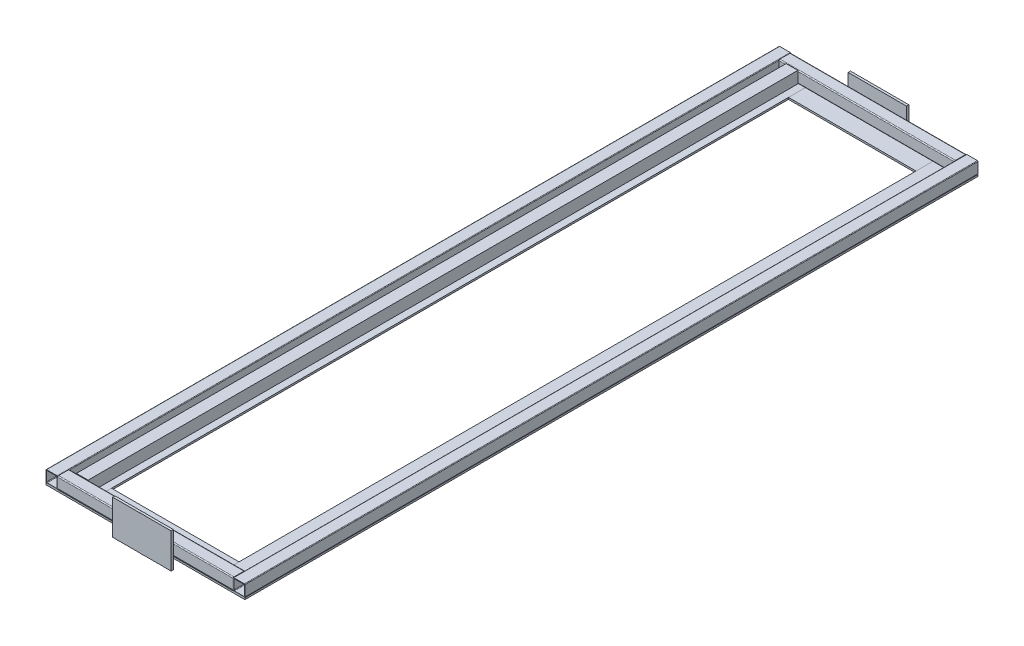
SolidWorks part; units mm, degrees
material "1023 碳钢板 (SS)"
ref_plane "前视基准面" through (0, 0, 0) normal (0, 0, 1) x (1, 0, 0)
ref_plane "上视基准面" through (0, 0, 0) normal (0, 1, 0) x (1, 0, 0)
ref_plane "右视基准面" through (0, 0, 0) normal (1, 0, 0) x (0, 0, -1)
sketch "草图1" plane through (0, 0, 0) normal (0, 0, 1) x (1, 0, 0)
  line L0 (-40, 45) -> (40, 45)
  line L1 (-45, 50) -> (45, 50)
  line L2 (-50, 45) -> (-50, -45)
  line L3 (-45, -50) -> (45, -50)
  line L4 (50, 45) -> (50, -45)
  line L5 (-50, 50) -> (50, -50) construction
  line L6 (-50, -50) -> (50, 50) construction
  line L7 (45, 40) -> (45, -40)
  line L8 (-40, -45) -> (40, -45)
  line L9 (-45, 40) -> (-45, -40)
  line L10 (-45, -45) -> (45, -45) construction
  line L11 (-45, 45) -> (-45, -45) construction
  line L12 (45, 45) -> (45, -45) construction
  line L13 (-45, 45) -> (45, 45) construction
  line L14 (-50, 50) -> (-50, -50) construction
  line L15 (-50, -50) -> (50, -50) construction
  line L16 (50, 50) -> (50, -50) construction
  line L17 (-50, 50) -> (50, 50) construction
  arc A0 (-40, -45) -> (-45, -40) centre (-40, -40) cw
  arc A1 (45, -40) -> (40, -45) centre (40, -40) cw
  arc A2 (40, 45) -> (45, 40) centre (40, 40) cw
  arc A3 (-40, 45) -> (-45, 40) centre (-40, 40) ccw
  arc A4 (-50, -45) -> (-45, -50) centre (-45, -45) ccw
  arc A5 (45, -50) -> (50, -45) centre (45, -45) ccw
  arc A6 (45, 50) -> (50, 45) centre (45, 45) cw
  arc A7 (-45, 50) -> (-50, 45) centre (-45, 45) ccw
  point P0 (0, 0)
  dimension "D4" = 5
  dimension "D5" = 5
  dimension "D1" = 100
  dimension "D2" = 100
  dimension "D3" = 5
extrude "凸台-拉伸1" add sketch "草图1" along normal blind 6265.6
pattern_linear "阵列(线性)1" count 2 spacing 1600 along (1, 0, 0) of bodies 106
sketch "草图2" plane through (50, 0, 0) normal (1, 0, 0) x (0, 0, -1)
  line L0 (-6265.6, -45) -> (-6265.6, 45) construction
  line L1 (-6173.6, -50) -> (-6257.6, -50)
  line L2 (-6165.6, -42) -> (-6165.6, 42)
  line L3 (-6173.6, 50) -> (-6257.6, 50)
  line L4 (-6265.6, -42) -> (-6265.6, 42)
  line L5 (-6165.6, -50) -> (-6265.6, 50) construction
  line L6 (-6165.6, 50) -> (-6265.6, -50) construction
  line L7 (-6265.6, 50) -> (0, 50) construction
  line L8 (-6265.6, -50) -> (0, -50) construction
  line L9 (-6175.6, 45) -> (-6255.6, 45)
  line L10 (-6260.6, -40) -> (-6260.6, 40)
  line L11 (-6175.6, -45) -> (-6255.6, -45)
  line L12 (-6170.6, -40) -> (-6170.6, 40)
  line L13 (-6260.6, -45) -> (-6260.6, 45) construction
  line L14 (-6170.6, -45) -> (-6260.6, -45) construction
  line L15 (-6170.6, -45) -> (-6170.6, 45) construction
  line L16 (-6170.6, 45) -> (-6260.6, 45) construction
  line L17 (-6165.6, -50) -> (-6265.6, -50) construction
  line L18 (-6265.6, -50) -> (-6265.6, 50) construction
  line L19 (-6165.6, -50) -> (-6165.6, 50) construction
  line L20 (-6165.6, 50) -> (-6265.6, 50) construction
  arc A0 (-6260.6, -40) -> (-6255.6, -45) centre (-6255.6, -40) ccw
  arc A1 (-6175.6, -45) -> (-6170.6, -40) centre (-6175.6, -40) ccw
  arc A2 (-6175.6, 45) -> (-6170.6, 40) centre (-6175.6, 40) cw
  arc A3 (-6255.6, 45) -> (-6260.6, 40) centre (-6255.6, 40) ccw
  arc A4 (-6257.6, -50) -> (-6265.6, -42) centre (-6257.6, -42) cw
  arc A5 (-6173.6, -50) -> (-6165.6, -42) centre (-6173.6, -42) ccw
  arc A6 (-6165.6, 42) -> (-6173.6, 50) centre (-6173.6, 42) ccw
  arc A7 (-6257.6, 50) -> (-6265.6, 42) centre (-6257.6, 42) ccw
  point P0 (-6215.6, 0)
  dimension "D3" = 5
  dimension "D4" = 8
  dimension "D1" = 100
  dimension "D2" = 5
extrude "凸台-拉伸2" add sketch "草图2" along normal up to surface (1500 mm away) separate body up to face at (1550, 0, 3132.8)
pattern_linear "阵列(线性)2" count 2 spacing 6165.6 along (0, 0, -1) of bodies 108
sketch "草图4" plane through (0, 0, 0) normal (0, 0, -1) x (-1, 0, 0)
  line L0 (50, 45) -> (50, -45) construction
  circle A0 centre (-790, 0) radius 150
  point P2 (50, 0)
  dimension "D1" = 300
  dimension "D2" = 840
extrude "凸台-拉伸4" add sketch "草图4" along normal blind 20 separate body
sketch "草图5" plane through (0, 0, 6265.6) normal (0, 0, 1) x (1, 0, 0)
  circle A0 centre (790, 0) radius 150
  dimension "D1" = 300
extrude "凸台-拉伸5" add sketch "草图5" along normal blind 20 separate body
sketch "草图6" plane through (0, 0, 6285.6) normal (0, 0, 1) x (1, 0, 0)
  circle A0 centre (790, 0) radius 140
  dimension "D1" = 280
extrude "切除-拉伸1" cut sketch "草图6" against normal blind 3
sketch "草图7" plane through (0, 0, -20) normal (0, 0, -1) x (-1, 0, 0)
  circle A0 centre (-790, 0) radius 90
  dimension "D1" = 180
extrude "切除-拉伸2" cut sketch "草图7" against normal blind 5
sketch "草图8" plane through (0, 0, -20) normal (0, 0, -1) x (-1, 0, 0)
  circle A0 centre (-790, 0) radius 127.5 construction
  circle A1 centre (-790, 127.5) radius 6.25
  dimension "D1" = 255
  dimension "D2" = 12.5
extrude "切除-拉伸3" cut sketch "草图8" against normal through all
pattern_circular "阵列(圆周)1" count 8 over 360 about axis through (790, 0, 6285.6) along (0, 0, -1) of "切除-拉伸3"
sketch "草图11" plane through (0, 0, -15) normal (0, 0, -1) x (-1, 0, 0)
  line L1 (-850, 30) -> (-730, 30)
  line L2 (-850, 30) -> (-850, -30)
  line L3 (-850, -30) -> (-730, -30)
  line L4 (-730, 30) -> (-730, -30)
  line L5 (-850, 30) -> (-730, -30) construction
  line L6 (-850, -30) -> (-730, 30) construction
  point P0 (-790, 0)
  dimension "D1" = 60
  dimension "D2" = 120
extrude "切除-拉伸5" [suppressed] cut sketch "草图11" against normal up to surface (115 mm away)
fillet "圆角1" [suppressed] radius 5
fillet "圆角2" [suppressed] radius 5
fillet "圆角3" [suppressed] radius 5
sketch "草图12" plane through (0, 50, 0) normal (0, 1, 0) x (1, 0, 0)
  line L0 (1555, -6265.6) -> (1555, 0) construction
  line L1 (50, -90) -> (1555, -90)
  line L2 (50, -90) -> (50, -2077.7459)
  line L3 (50, -2077.7459) -> (1555, -2077.7459)
  line L4 (1555, -90) -> (1555, -2077.7459)
extrude "凸台-拉伸8" [suppressed] add sketch "草图12" along normal blind 36 separate body
ref_axis "基准轴1" through (790, 0, 6285.6) along (0, 0, -1)
sketch "草图21" plane through (0, 0, -20) normal (0, 0, -1) x (-1, 0, 0)
  line L1 (-1040, 150) -> (-540, 150)
  line L2 (-1040, 150) -> (-1040, -150)
  line L3 (-1040, -150) -> (-540, -150)
  line L4 (-540, 150) -> (-540, -150)
  line L5 (-1040, 150) -> (-540, -150) construction
  line L6 (-1040, -150) -> (-540, 150) construction
  point P0 (-790, 0)
  dimension "D1" = 300
  dimension "D2" = 500
extrude "凸台-拉伸11" add sketch "草图21" against normal blind 20
sketch "草图22" plane through (0, 0, 6285.6) normal (0, 0, 1) x (1, 0, 0)
  line L0 (1040, 150) -> (1040, 42) construction
  line L1 (540, -148.5061) -> (1040, -148.5061)
  line L2 (540, -148.5061) -> (540, 148.5061)
  line L3 (540, 148.5061) -> (1040, 148.5061)
  line L4 (1040, -148.5061) -> (1040, 148.5061)
  line L5 (540, -148.5061) -> (1040, 148.5061) construction
  line L6 (540, 148.5061) -> (1040, -148.5061) construction
  point P0 (790, 0)
extrude "凸台-拉伸13" add sketch "草图22" against normal blind 20
ref_plane "基准面1" through (0, 0, 3132.8) normal (0, 0, 1) x (1, 0, 0)
ref_plane "基准面2" through (800, 0, 0) normal (-1, 0, 0) x (0, 0, 1)
sketch "草图23" plane through (0, 0, 100) normal (0, 0, 1) x (1, 0, 0)
  line L0 (800, 0) -> (550, 0) construction
  line L1 (1550, -50) -> (50, -50) construction
  line L2 (500, 50) -> (600, 50)
  line L3 (500, 50) -> (500, -50)
  line L4 (500, -50) -> (600, -50)
  line L5 (600, 50) -> (600, -50)
  line L6 (500, 50) -> (600, -50) construction
  line L7 (500, -50) -> (600, 50) construction
  line L8 (800, 0) -> (800, 362.3547) construction
  line L9 (1000, 50) -> (1100, 50)
  line L10 (1000, 50) -> (1000, -50)
  line L11 (1000, -50) -> (1100, -50)
  line L12 (1100, 50) -> (1100, -50)
  line L13 (1000, 50) -> (1100, -50) construction
  line L14 (1000, -50) -> (1100, 50) construction
  line L15 (800, 586.0493) -> (800, -586.0493) construction
  point P10 (1050, 0)
  dimension "D1" = 600
extrude "凸台-拉伸14" [suppressed] add sketch "草图23" along normal up to surface (6065.6 mm away)
sketch "草图24" plane through (0, -50, 0) normal (0, 1, 0) x (1, 0, 0)
  line L0 (540, 0) -> (50, 0) construction
  line L1 (1650, -6265.6) -> (1360, -6265.6)
  line L2 (1650, -6265.6) -> (1650, 0)
  line L3 (1650, 0) -> (1360, 0)
  line L4 (1360, -6265.6) -> (1360, 0)
  line L7 (1650, -6265.6) -> (1650, 0) construction
  line L8 (1645, -6265.6) -> (1650, -6265.6) construction
  dimension "D1" = 290
extrude "凸台-拉伸16" add sketch "草图24" against normal blind 15 separate body
sketch "草图26" [suppressed] plane through (950, 0, 0) normal (-1, 0, 0) x (0, 0, 1)
  line L0 (6165.6, -50) -> (100, -50) construction
  line L1 (632.8, -50) -> (732.8, -50)
  line L2 (632.8, -50) -> (632.8, 50)
  line L3 (632.8, 50) -> (732.8, 50)
  line L4 (732.8, -50) -> (732.8, 50)
  line L5 (6165.6, 50) -> (100, 50) construction
  line L6 (3132.8, -50) -> (3132.8, 50) construction
  line L7 (5632.8, -50) -> (5532.8, -50)
  line L8 (5632.8, -50) -> (5632.8, 50)
  line L9 (5632.8, 50) -> (5532.8, 50)
  line L10 (5532.8, -50) -> (5532.8, 50)
  line L11 (6265.6, 50) -> (0, 50) construction
  line L12 (6265.6, -50) -> (0, -50) construction
  line L13 (3082.8, 50) -> (3182.8, 50)
  line L14 (3082.8, 50) -> (3082.8, -50)
  line L15 (3082.8, -50) -> (3182.8, -50)
  line L16 (3182.8, 50) -> (3182.8, -50)
  line L17 (3082.8, 50) -> (3182.8, -50) construction
  line L18 (3082.8, -50) -> (3182.8, 50) construction
  point P17 (3132.8, 0)
  dimension "D1" = 5000
extrude "凸台-拉伸17" [suppressed] add sketch "草图26" along normal up to surface (400 mm away)
sketch "草图27" plane through (0, -50, 0) normal (0, -1, 0) x (1, 0, 0)
  line L1 (1360, 6265.6) -> (270, 6265.6)
  line L2 (1360, 6265.6) -> (1360, 6025.6)
  line L3 (1360, 6025.6) -> (270, 6025.6)
  line L4 (270, 6265.6) -> (270, 6025.6)
  line L5 (-50, 6265.6) -> (-50, 0) construction
  line L6 (1360, 0) -> (270, 0)
  line L7 (1360, 0) -> (1360, 240)
  line L8 (1360, 240) -> (270, 240)
  line L9 (270, 0) -> (270, 240)
  dimension "D1" = 240
  dimension "D2" = 320
extrude "凸台-拉伸18" add sketch "草图27" along normal blind 15 separate body
sketch "草图28" plane through (0, 0, 6165.6) normal (0, 0, -1) x (-1, 0, 0)
  line L0 (-1550, -50) -> (-50, -50) construction
  line L1 (-110, -50) -> (-210, -50)
  line L2 (-110, -50) -> (-110, 50)
  line L3 (-110, 50) -> (-210, 50)
  line L4 (-210, -50) -> (-210, 50)
  line L5 (-1550, 50) -> (-50, 50) construction
  line L6 (-1360, -50) -> (-270, -50) construction
  line L7 (50, 45) -> (50, -45) construction
  dimension "D1" = 160
extrude "凸台-拉伸19" add sketch "草图28" along normal up to surface (6065.6 mm away) up to face at (800, 0, 100)
sketch "草图29" plane through (0, -65, 0) normal (0, -1, 0) x (1, 0, 0)
  line L0 (540, 0) -> (50, 0) construction
  line L1 (270, 6265.6) -> (-50, 6265.6)
  line L2 (270, 6265.6) -> (270, 0)
  line L3 (270, 0) -> (-50, 0)
  line L4 (-50, 6265.6) -> (-50, 0)
  line L5 (-50, 6265.6) -> (-50, 0) construction
extrude "凸台-拉伸21" add sketch "草图29" against normal blind 15 separate body
